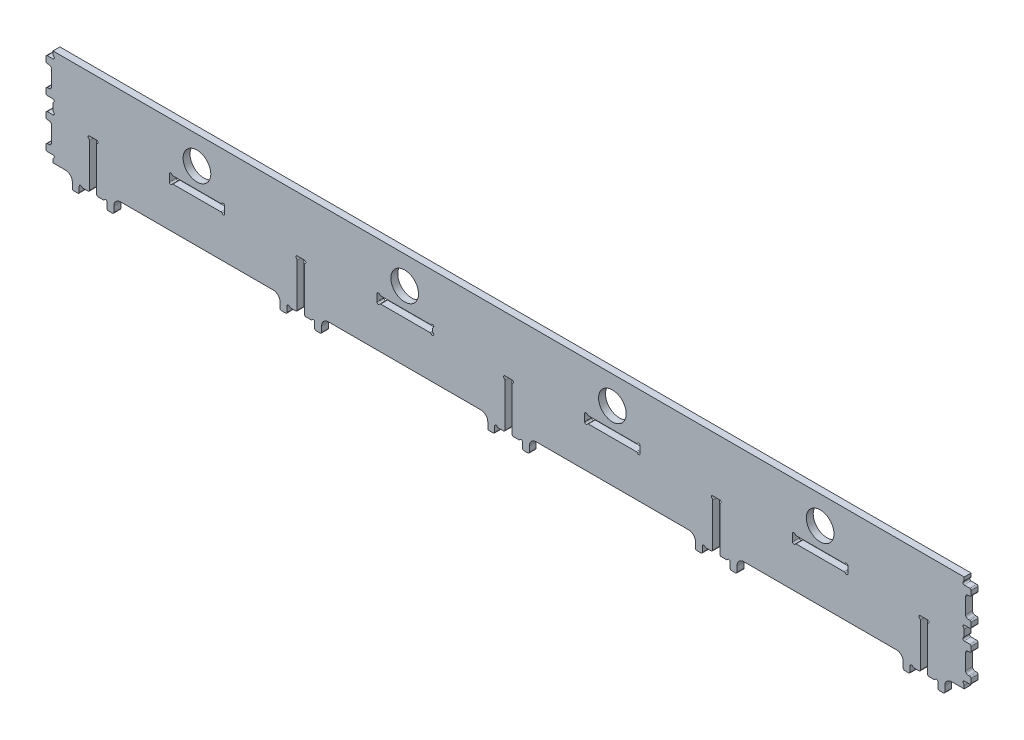
SolidWorks part; units mm, degrees
material "Plain Carbon Steel"
ref_plane "Front Plane" through (0, 0, 0) normal (0, 0, 1) x (1, 0, 0)
ref_plane "Top Plane" through (0, 0, 0) normal (0, 1, 0) x (1, 0, 0)
ref_plane "Right Plane" through (0, 0, 0) normal (1, 0, 0) x (0, 0, -1)
sketch "Sketch1" plane through (0, 0, 0) normal (0, 0, 1) x (1, 0, 0)
  line L1 (-329, 80) -> (329, 80)
  line L2 (-329, 80) -> (-329, 0)
  line L3 (-329, 0) -> (329, 0)
  line L4 (329, 80) -> (329, 0)
  point P4 (0, 0)
  dimension "D1" = 658
  dimension "D2" = 80
extrude "Boss-Extrude1" add sketch "Sketch1" along normal mid plane 5
sketch "Sketch2" plane through (0, 0, 0) normal (0, 0, 1) x (1, 0, 0)
  line L0 (-329, 0) -> (329, 0) construction
  line L1 (-15, 0) -> (-135, 0)
  line L2 (-15, 0) -> (-15, 5)
  line L3 (-20, 10) -> (-130, 10)
  line L4 (-135, 0) -> (-135, 5)
  line L5 (-165, 0) -> (-285, 0)
  line L6 (-165, 0) -> (-165, 5)
  line L7 (-170, 10) -> (-280, 10)
  line L8 (-285, 0) -> (-285, 5)
  line L9 (-315, 0) -> (-329, 0)
  line L10 (-315, 0) -> (-315, 5)
  line L11 (-320, 10) -> (-329, 10)
  line L12 (-329, 0) -> (-329, 10)
  line L13 (0, -55) -> (0, 55) construction
  line L14 (-329, 80) -> (-329, 0) construction
  arc A0 (-320, 10) -> (-315, 5) centre (-320, 5) cw
  arc A1 (-285, 5) -> (-280, 10) centre (-280, 5) cw
  arc A2 (-170, 10) -> (-165, 5) centre (-170, 5) cw
  arc A3 (-135, 5) -> (-130, 10) centre (-130, 5) cw
  arc A4 (-20, 10) -> (-15, 5) centre (-20, 5) cw
  point P16 (-285, 2.5)
  point P19 (-75, 0)
  point P30 (-135, 2.5)
  dimension "D7" = 5
  dimension "D1" = 15
  dimension "D2" = 135
  dimension "D3" = 30
  dimension "D4" = 30
  dimension "D5" = 150
  dimension "D6" = 10
extrude "Cut-Extrude1" cut sketch "Sketch2" along normal mid plane 5
mirror "Mirror1" about plane through (0, 0, 0) normal (1, 0, 0) of "Cut-Extrude1"
sketch "Sketch3" plane through (0, 0, 0) normal (0, 0, 1) x (1, 0, 0)
  line L0 (0, -2.75) -> (0, 2.75) construction
  line L1 (54.9, 45.2) -> (95.1, 45.2)
  line L2 (54.9, 45.2) -> (54.9, 40)
  line L3 (54.9, 40) -> (95.1, 40)
  line L4 (95.1, 45.2) -> (95.1, 40)
  line L5 (54.9, 45.2) -> (95.1, 40) construction
  line L6 (54.9, 40) -> (95.1, 45.2) construction
  line L7 (205, 45.2) -> (245, 45.2)
  line L8 (205, 45.2) -> (205, 40)
  line L9 (205, 40) -> (245, 40)
  line L10 (245, 45.2) -> (245, 40)
  line L11 (205, 45.2) -> (245, 40) construction
  line L12 (205, 40) -> (245, 45.2) construction
  line L13 (20, 10) -> (130, 10) construction
  line L14 (140, -5) -> (160, -5)
  line L15 (-10, -5) -> (10, -5)
  line L16 (-10, -5) -> (-10, 5)
  line L17 (-10, 5) -> (10, 5)
  line L18 (10, -5) -> (10, 5)
  line L19 (-10, -5) -> (10, 5) construction
  line L20 (-10, 5) -> (10, -5) construction
  line L21 (140, -5) -> (140, 5)
  line L22 (140, 5) -> (160, 5)
  line L23 (160, -5) -> (160, 5)
  line L24 (140, -5) -> (160, 5) construction
  line L25 (140, 5) -> (160, -5) construction
  line L26 (290, -5) -> (310, -5)
  line L27 (290, -5) -> (290, 5)
  line L28 (290, 5) -> (310, 5)
  line L29 (310, -5) -> (310, 5)
  line L30 (290, -5) -> (310, 5) construction
  line L31 (290, 5) -> (310, -5) construction
  point P0 (75, 42.6)
  point P5 (225, 42.6)
  point P14 (0, 0)
  point P21 (150, 0)
  point P26 (300, 0)
  dimension "D1" = 75
  dimension "D2" = 150
  dimension "D3" = 40.2
  dimension "D4" = 40
  dimension "D5" = 5.2
  dimension "D6" = 30
  dimension "D7" = 20
  dimension "D8" = 10
  dimension "D9" = 3
extrude "Cut-Extrude2" cut sketch "Sketch3" against normal mid plane 5
mirror "Mirror2" about plane through (0, 0, 0) normal (1, 0, 0) of "Cut-Extrude2"
sketch "Sketch4" plane through (0, 0, 0) normal (0, 0, 1) x (1, 0, 0)
  line L0 (2.75, 0) -> (-2.75, 0) construction
  line L1 (-2.6, 40) -> (2.6, 40)
  line L2 (-2.6, 40) -> (-2.6, 0)
  line L3 (-2.6, 0) -> (2.6, 0)
  line L4 (2.6, 40) -> (2.6, 0)
  line L5 (-2.6, 40) -> (2.6, 0) construction
  line L6 (-2.6, 0) -> (2.6, 40) construction
  line L7 (0, -2.75) -> (0, 2.75) construction
  point P0 (0, 20)
  dimension "D1" = 40
  dimension "D2" = 5.2
extrude "Cut-Extrude3" cut sketch "Sketch4" against normal through all both and the other way through all
pattern_linear "LPattern1" count 3 spacing 150 along (1, 0, 0) of "Cut-Extrude3"
mirror "Mirror3" about plane through (0, 0, 0) normal (1, 0, 0) of "LPattern1"
sketch "Sketch5" plane through (0, 0, 2.5) normal (0, 0, 1) x (1, 0, 0)
  line L0 (-245, 45.2) -> (-205, 45.2) construction
  line L1 (-205, 40) -> (-245, 40) construction
  line L2 (-205, 45.2) -> (-205, 40) construction
  circle A6 centre (-55, 40) radius 1
  circle A7 centre (-55, 45) radius 1
  circle A16 centre (-244, 45.2) radius 1
  circle A17 centre (-244, 40) radius 1
  circle A18 centre (-206, 45.2) radius 1
  circle A19 centre (-206, 40) radius 1
  circle A20 centre (-94, 45.2) radius 1
  circle A21 centre (-94, 40) radius 1
  circle A24 centre (56, 45.2) radius 1
  circle A25 centre (56, 40) radius 1
  circle A26 centre (94, 45.2) radius 1
  circle A27 centre (94, 40) radius 1
  circle A28 centre (206, 45.2) radius 1
  circle A29 centre (206, 40) radius 1
  circle A30 centre (244, 45.2) radius 1
  circle A31 centre (244, 40) radius 1
  circle A32 centre (-56, 45.2) radius 1 [skipped]
  circle A33 centre (-56, 40) radius 1 [skipped]
  dimension "D1" = 2
  dimension "D2" = 4
extrude "Cut-Extrude4" cut sketch "Sketch5" against normal through all
fillet "Fillet1" radius 1 17 edges at (-54.9, 44.005, 0) (-55.9798, 45.2, 0) (-56, 40, 0) (243, 40, 0) (207, 40, 0) (243, 45.2, 0) (207, 45.2, 0) (57, 45.2, 0) (93, 45.2, 0) (93, 40, 0) (57, 40, 0) (-93, 40, 0) (-93, 45.2, 0) (-207, 45.2, 0) (-207, 40, 0) (-243, 45.2, 0) (-243, 40, 0)
sketch "Sketch6" plane through (0, 0, 2.5) normal (0, 0, 1) x (1, 0, 0)
  line L0 (-302.6, 5) -> (-302.6, 40) construction
  line L1 (-297.4, 40) -> (-297.4, 5) construction
  circle A10 centre (-302.6, 39) radius 1
  circle A11 centre (-297.4, 39) radius 1
  circle A12 centre (-152.6, 39) radius 1
  circle A13 centre (-147.4, 39) radius 1
  circle A14 centre (-2.6, 39) radius 1
  circle A15 centre (2.6, 39) radius 1
  circle A16 centre (147.4, 39) radius 1
  circle A17 centre (152.6, 39) radius 1
  circle A18 centre (297.4, 39) radius 1
  circle A19 centre (302.6, 39) radius 1
  dimension "D1" = 2
extrude "Cut-Extrude5" cut sketch "Sketch6" against normal through all
fillet "Fillet2" radius 1 10 edges at (302.6, 38, 0) (297.4, 38, 0) (152.6, 38, 0) (147.4, 38, 0) (2.6, 38, 0) (-2.6, 38, 0) (-147.4, 38, 0) (-152.6, 38, 0) (-297.4, 38, 0) (-302.6, 38, 0)
fillet "Fillet6" radius 1 30 edges at (315, 0, 0) (302.6, 5, 0) (297.4, 5, 0) (310, 0, 0) (290, 0, 0) (285, 0, 0) (165, 0, 0) (160, 0, 0) (152.6, 5, 0) (147.4, 5, 0) (140, 0, 0) (135, 0, 0) (-147.4, 5, 0) (15, 0, 0) (10, 0, 0) (2.6, 5, 0) (-2.6, 5, 0) (-10, 0, 0) (-15, 0, 0) (-135, 0, 0) (-140, 0, 0) (-152.6, 5, 0) (-165, 0, 0) (-160, 0, 0) (-285, 0, 0) (-290, 0, 0) (-297.4, 5, 0) (-302.6, 5, 0) (-310, 0, 0) (-315, 0, 0)
sketch "Sketch11" plane through (0, 0, 2.5) normal (0, 0, 1) x (1, 0, 0)
  line L0 (-310, 5) -> (-303.6, 5) construction
  line L1 (-296.4, 5) -> (-290, 5) construction
  circle A0 centre (-309, 5) radius 1
  circle A1 centre (-291, 5) radius 1
  circle A2 centre (-159, 5) radius 1
  circle A3 centre (-141, 5) radius 1
  circle A4 centre (-9, 5) radius 1
  circle A5 centre (9, 5) radius 1
  circle A6 centre (141, 5) radius 1
  circle A7 centre (159, 5) radius 1
  circle A8 centre (291, 5) radius 1
  circle A9 centre (309, 5) radius 1
  dimension "D1" = 2
extrude "Cut-Extrude9" cut sketch "Sketch11" against normal through all
fillet "Fillet7" radius 1 10 edges at (308, 5, 0) (292, 5, 0) (158, 5, 0) (142, 5, 0) (8, 5, 0) (-8, 5, 0) (-142, 5, 0) (-158, 5, 0) (-292, 5, 0) (-308, 5, 0)
sketch "Sketch12" plane through (-329, 0, 0) normal (-1, 0, 0) x (0, 0, 1)
  line L0 (-2.5, 80) -> (-2.5, 10) construction
  line L1 (-2.5, 75) -> (2.5, 75)
  line L2 (-2.5, 75) -> (-2.5, 50)
  line L3 (-2.5, 50) -> (2.5, 50)
  line L4 (2.5, 75) -> (2.5, 50)
  line L5 (2.5, 80) -> (2.5, 10) construction
  line L6 (2.5, 80) -> (-2.5, 80) construction
  line L7 (-2.5, 40) -> (2.5, 40)
  line L8 (-2.5, 40) -> (-2.5, 15)
  line L9 (-2.5, 15) -> (2.5, 15)
  line L10 (2.5, 40) -> (2.5, 15)
  line L11 (2.5, 10) -> (-2.5, 10) construction
  dimension "D1" = 5
  dimension "D2" = 25
  dimension "D3" = 5
  dimension "D4" = 25
extrude "Boss-Extrude3" add sketch "Sketch12" along normal blind 5
sketch "Sketch13" plane through (-334, 0, 0) normal (-1, 0, 0) x (0, 0, 1)
  line L0 (-2.5, 75) -> (-2.5, 50) construction
  line L1 (-2.5, 70) -> (2.5, 70)
  line L2 (-2.5, 70) -> (-2.5, 55)
  line L3 (-2.5, 55) -> (2.5, 55)
  line L4 (2.5, 70) -> (2.5, 55)
  line L5 (2.5, 50) -> (2.5, 75) construction
  line L6 (-2.5, 40) -> (-2.5, 15) construction
  line L7 (-2.5, 35) -> (2.5, 35)
  line L8 (-2.5, 35) -> (-2.5, 20)
  line L9 (-2.5, 20) -> (2.5, 20)
  line L10 (2.5, 35) -> (2.5, 20)
  line L11 (2.5, 15) -> (2.5, 40) construction
  line L12 (2.5, 75) -> (-2.5, 75) construction
  line L13 (-2.5, 50) -> (2.5, 50) construction
  line L14 (2.5, 40) -> (-2.5, 40) construction
  line L15 (-2.5, 15) -> (2.5, 15) construction
  point P22 (0, 20)
  dimension "D1" = 5
  dimension "D2" = 5
  dimension "D3" = 5
  dimension "D4" = 5
extrude "Cut-Extrude10" cut sketch "Sketch13" against normal blind 4
mirror "Mirror5" about plane through (0, 0, 0) normal (1, 0, 0) of "Cut-Extrude10", "Boss-Extrude3"
fillet "Fillet8" radius 2 8 edges at (330, 20, 0) (330, 35, 0) (330, 55, 0) (330, 70, 0) (-330, 20, 0) (-330, 35, 0) (-330, 70, 0) (-330, 55, 0)
sketch "Sketch14" plane through (0, 0, 2.5) normal (0, 0, 1) x (1, 0, 0)
  line L0 (-329, 80) -> (-329, 75) construction
  line L1 (-329, 50) -> (-329, 40) construction
  line L2 (-329, 15) -> (-329, 10) construction
  line L3 (0, -2.75) -> (0, 2.75) construction
  circle A0 centre (-329, 76) radius 1
  circle A1 centre (-329, 49) radius 1
  circle A2 centre (-329, 41) radius 1
  circle A3 centre (-329, 14) radius 1
  circle A4 centre (329, 14) radius 1
  circle A5 centre (329, 41) radius 1
  circle A6 centre (329, 49) radius 1
  circle A7 centre (329, 76) radius 1
  dimension "D1" = 2
extrude "Cut-Extrude11" cut sketch "Sketch14" against normal through all
fillet "Fillet9" radius 1 24 edges at (-329, 13, 0) (-334, 15, 0) (-334, 20, 0) (-334, 35, 0) (-334, 40, 0) (-329, 42, 0) (-329, 48, 0) (-334, 50, 0) (-334, 55, 0) (-334, 70, 0) (-334, 75, 0) (-329, 77, 0) (329, 77, 0) (334, 75, 0) (334, 70, 0) (334, 55, 0) (334, 50, 0) (329, 48, 0) (329, 42, 0) (334, 40, 0) (334, 35, 0) (334, 20, 0) (334, 15, 0) (329, 13, 0)
sketch "Sketch16" plane through (0, 0, 2.5) normal (0, 0, 1) x (1, 0, 0)
  line L0 (329, 80) -> (-329, 80) construction
  line L1 (0, -2.75) -> (0, 2.75) construction
  circle A0 centre (-75, 60) radius 10
  circle A1 centre (-225, 60) radius 10
  circle A2 centre (225, 60) radius 10
  circle A3 centre (75, 60) radius 10
  dimension "D1" = 20
  dimension "D2" = 20
  dimension "D3" = 75
extrude "Cut-Extrude13" cut sketch "Sketch16" against normal through all
